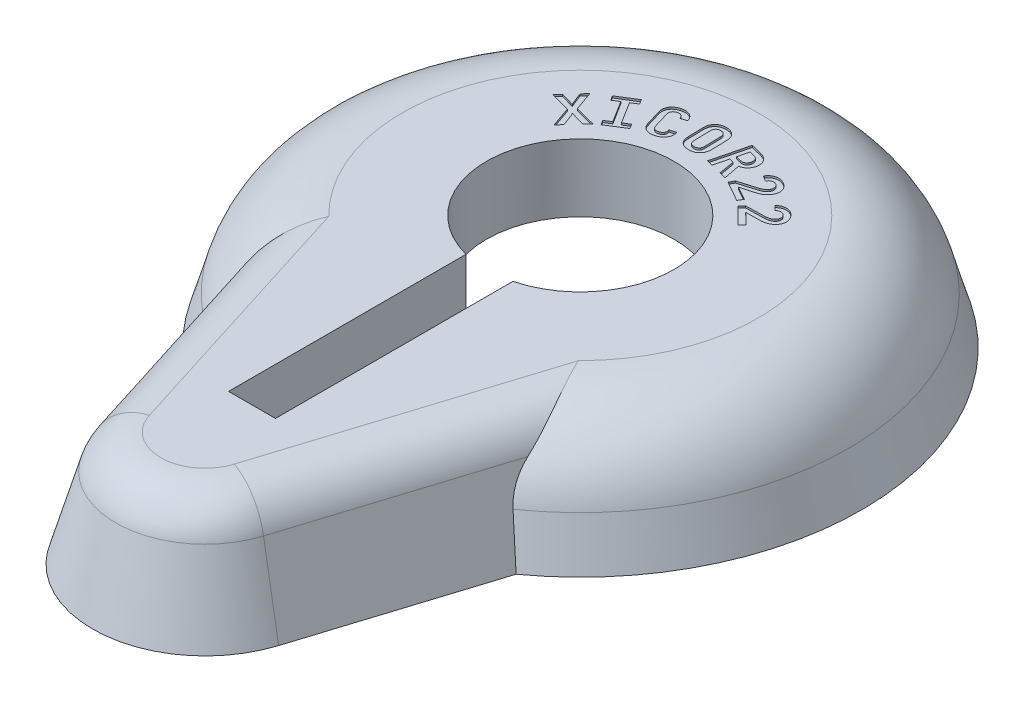
SolidWorks part; units mm, degrees
material "Brass"
ref_plane "Front Plane" through (0, 0, 0) normal (0, 0, 1) x (1, 0, 0)
ref_plane "Top Plane" through (0, 0, 0) normal (0, 1, 0) x (1, 0, 0)
ref_plane "Right Plane" through (0, 0, 0) normal (1, 0, 0) x (0, 0, -1)
sketch "Sketch1" plane through (0, 0, 0) normal (0, 1, 0) x (1, 0, 0)
  line L0 (0, 35.7592) -> (0, -31.5719) construction
  line L1 (-22.2438, -11.7045) -> (-14.5346, -36.1547)
  line L2 (14.5346, -36.1547) -> (22.2438, -11.7045)
  arc A0 (-14.5346, -36.1547) -> (14.5346, -36.1547) centre (0, -31.5719) ccw
  arc A1 (-22.2438, -11.7045) -> (22.2438, -11.7045) centre (0, 19.2281) cw
  point P9 (0, 0)
  point P10 (0, 0)
  point P11 (0, 0)
  point P12 (0, 0)
  point P13 (0, 0)
  point P14 (0, 0)
  point P15 (0, 0)
  point P16 (0, -32.5769)
  dimension "D1" = 38.1
  dimension "D2" = 15.24
  dimension "D3" = 50.8
  dimension "D4" = 35
extrude "Boss-Extrude2" add sketch "Sketch1" along normal blind 15.494 draft 16
fillet "Fillet1" radius 6.35 3 edges at (0, 15.494, 42.3691) (14.3818, 15.494, 21.8648) (-14.3818, 15.494, 21.8648)
fillet "Fillet2" radius 12.7 1 edges at (0, 15.494, -52.8853)
sketch "Sketch3" plane through (0, 0, 0) normal (0, -1, 0) x (1, 0, 0)
  line L4 (20.0801, 10.1199) -> (12.1122, 35.3909)
  line L5 (-12.1122, 35.3909) -> (-20.0801, 10.1199)
  line L6 (20.0801, 10.1199) -> (12.1122, 35.3909)
  line L7 (-12.1122, 35.3909) -> (-20.0801, 10.1199)
  arc A4 (-20.0801, 10.1199) -> (20.0801, 10.1199) centre (0, -19.2281) ccw
  arc A5 (12.1122, 35.3909) -> (-12.1122, 35.3909) centre (0, 31.5719) ccw
  arc A6 (-20.0801, 10.1199) -> (20.0801, 10.1199) centre (0, -19.2281) ccw
  arc A7 (12.1122, 35.3909) -> (-12.1122, 35.3909) centre (0, 31.5719) ccw
  dimension "D1" = 2.54
extrude "Cut-Extrude1" cut sketch "Sketch3" against normal blind 6.35 contours A6 L6 A7 L7
sketch "Sketch4" plane through (0, 15.494, 0) normal (0, 1, 0) x (1, 0, 0)
  circle A0 centre (0, 19.2281) radius 12.7
extrude "Cut-Extrude2" cut sketch "Sketch4" against normal through all
sketch "Sketch5" plane through (0, 15.494, 0) normal (0, 1, 0) x (1, 0, 0)
  line L0 (0, 19.2281) -> (0, -31.5719) construction
  line L1 (-3.175, 19.2281) -> (3.175, 19.2281)
  line L2 (-3.175, 19.2281) -> (-3.175, -25.2219)
  line L3 (-3.175, -25.2219) -> (3.175, -25.2219)
  line L4 (3.175, 19.2281) -> (3.175, -25.2219)
  line L5 (-3.175, 19.2281) -> (3.175, -25.2219) construction
  line L6 (-3.175, -25.2219) -> (3.175, 19.2281) construction
  point P0 (0, -2.9969)
  point P7 (0, 19.2281)
  dimension "D1" = 50.8
  dimension "D2" = 44.45
  dimension "D3" = 6.35
extrude "Cut-Extrude4" cut sketch "Sketch5" against normal blind 6.35
sketch "Sketch6" plane through (0, 15.494, 0) normal (0, 1, 0) x (1, 0, 0)
  text T0 "<b>XICOR22  </b>" font "JetBrainsMono NF" height in points 14
  point P1 (-15.1373, 20.9941)
  point P2 (15.1374, 20.9941)
extrude "Cut-Extrude9" cut sketch "Sketch6" against normal blind 0.254
